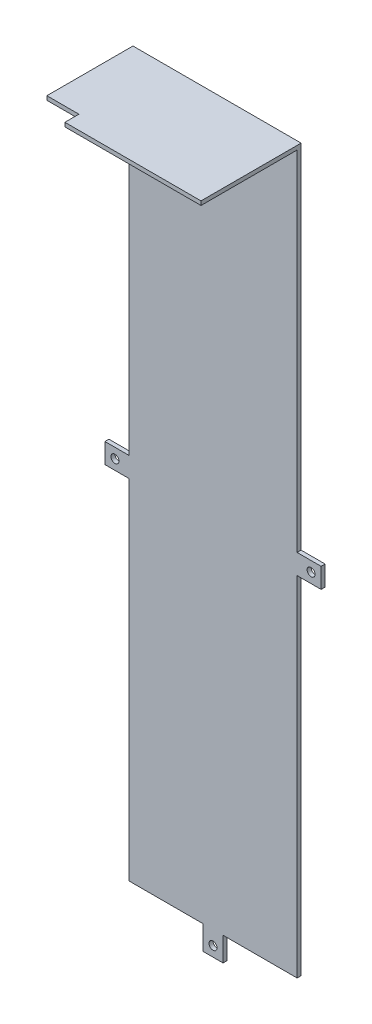
SolidWorks part; units mm, degrees
ref_plane "Alzado" through (0, 0, 0) normal (0, 0, 1) x (1, 0, 0)
ref_plane "Planta" through (0, 0, 0) normal (0, 1, 0) x (1, 0, 0)
ref_plane "Vista lateral" through (0, 0, 0) normal (1, 0, 0) x (0, 0, -1)
sketch "Sketch1" plane through (0, 0, 0) normal (0, 1, 0) x (1, 0, 0)
  line L1 (-16.6842, 5.7368) -> (25.3158, 5.7368)
  line L2 (-16.6842, 5.7368) -> (-16.6842, -19.2632)
  line L3 (-16.6842, -19.2632) -> (25.3158, -19.2632)
  line L4 (25.3158, 5.7368) -> (25.3158, -19.2632)
  dimension "D1" = 42
  dimension "D2" = 25
extrude "Boss-Extrude1" add sketch "Sketch1" along normal blind 1
sketch "Sketch2" plane through (0, 1, 0) normal (0, 1, 0) x (1, 0, 0)
  line L0 (-16.6842, 5.7368) -> (-16.6842, -19.2632) construction
  line L1 (25.3158, 5.7368) -> (-16.6842, 5.7368)
  line L2 (25.3158, 5.7368) -> (25.3158, 4.7368)
  line L3 (25.3158, 4.7368) -> (-16.6842, 4.7368)
  line L4 (-16.6842, 5.7368) -> (-16.6842, 4.7368)
  dimension "D1" = 1
extrude "Boss-Extrude2" add sketch "Sketch2" against normal blind 179
sketch "Sketch3" plane through (0, -178, 0) normal (0, -1, 0) x (1, 0, 0)
  line L1 (25.3158, -5.7368) -> (-16.6842, -5.7368)
  line L2 (25.3158, -5.7368) -> (25.3158, -4.7368)
  line L3 (25.3158, -4.7368) -> (-16.6842, -4.7368)
  line L4 (-16.6842, -5.7368) -> (-16.6842, -4.7368)
extrude "Boss-Extrude3" add sketch "Sketch3" along normal blind 2.1
sketch "Sketch4" plane through (0, 0, -4.7368) normal (0, 0, 1) x (1, 0, 0)
  line L0 (-16.6842, -180.1) -> (-16.6842, 0) construction
  line L1 (25.3158, -180.1) -> (-16.6842, -180.1)
  line L2 (25.3158, -180.1) -> (25.3158, -179.1)
  line L3 (25.3158, -179.1) -> (-16.6842, -179.1)
  line L4 (-16.6842, -180.1) -> (-16.6842, -179.1)
  dimension "D1" = 1
extrude "Boss-Extrude4" add sketch "Sketch4" along normal blind 15
sketch "Sketch6" plane through (0, -180.1, 0) normal (0, -1, 0) x (1, 0, 0)
  line L0 (-16.6842, 10.2632) -> (-16.6842, -5.7368) construction
  line L2 (25.3158, -5.7368) -> (25.3158, 10.2632) construction
  circle A0 centre (-6.6842, 3.5932) radius 1.25
  circle A1 centre (15.3158, 3.5932) radius 1.25
  dimension "D2" = 10
  dimension "D1" = 10
extrude "Cut-Extrude1" cut sketch "Sketch6" against normal blind 15
sketch "Sketch7" plane through (0, -180.1, 0) normal (0, -1, 0) x (1, 0, 0)
  line L1 (25.3158, -5.7368) -> (25.3158, 10.2632) construction
  line L2 (-16.6842, 10.2632) -> (25.3158, 10.2632)
  line L3 (-16.6842, 10.2632) -> (-16.6842, 8.5932)
  line L4 (-16.6842, 8.5932) -> (25.3158, 8.5932)
  line L5 (25.3158, 10.2632) -> (25.3158, 8.5932)
extrude "Cut-Extrude2" cut sketch "Sketch7" against normal blind 15
sketch "Sketch8" plane through (0, 1, 0) normal (0, 1, 0) x (1, 0, 0)
  line L1 (-16.6842, -19.2632) -> (-8.6842, -19.2632)
  line L2 (-16.6842, -19.2632) -> (-16.6842, -15.7632)
  line L3 (-16.6842, -15.7632) -> (-8.6842, -15.7632)
  line L4 (-8.6842, -19.2632) -> (-8.6842, -15.7632)
  dimension "D1" = 8
  dimension "D2" = 3.5
extrude "Cut-Extrude3" cut sketch "Sketch8" against normal blind 15
sketch "Sketch9" plane through (0, -180.1, 0) normal (0, -1, 0) x (1, 0, 0)
  line L1 (-16.6842, 8.5932) -> (25.3158, 8.5932)
  line L2 (-16.6842, 8.5932) -> (-16.6842, -5.7368)
  line L3 (-16.6842, -5.7368) -> (25.3158, -5.7368)
  line L4 (25.3158, 8.5932) -> (25.3158, -5.7368)
extrude "Cut-Extrude4" cut sketch "Sketch9" against normal blind 10
sketch "Sketch10" plane through (0, 0, -5.7368) normal (0, 0, -1) x (-1, 0, 0)
  line L0 (-25.3158, -170.1) -> (-6.8158, -170.1) construction
  line L1 (16.6842, -170.1) -> (-25.3158, -170.1) construction
  line L3 (-6.8158, -170.1) -> (-1.8158, -170.1)
  line L4 (-6.8158, -170.1) -> (-6.8158, -176.1)
  line L5 (-6.8158, -176.1) -> (-1.8158, -176.1)
  line L6 (-1.8158, -170.1) -> (-1.8158, -176.1)
  dimension "D1" = 18.5
  dimension "D2" = 6
  dimension "D3" = 5
extrude "Boss-Extrude5" add sketch "Sketch10" against normal blind 1
sketch "Sketch11" plane through (0, 0, -5.7368) normal (0, 0, -1) x (-1, 0, 0)
  line L0 (-6.8158, -176.1) -> (-6.8158, -171.1) construction
  line L1 (-6.8158, -170.1) -> (-6.8158, -176.1) construction
  line L2 (-6.8158, -171.1) -> (-1.8158, -171.1) construction
  line L3 (-1.8158, -176.1) -> (-1.8158, -170.1) construction
  line L4 (-1.8158, -171.1) -> (-1.8158, -176.1) construction
  line L5 (-1.8158, -176.1) -> (-6.8158, -176.1) construction
  circle A0 centre (-4.3158, -173.6) radius 1
  dimension "D1" = 5
extrude "Cut-Extrude5" cut sketch "Sketch11" against normal blind 1
sketch "Sketch12" plane through (0, -170.1, 0) normal (0, -1, 0) x (1, 0, 0)
  line L1 (25.3158, -5.7368) -> (-16.6842, -5.7368)
  line L2 (25.3158, -5.7368) -> (25.3158, -4.7368)
  line L3 (25.3158, -4.7368) -> (-16.6842, -4.7368)
  line L4 (-16.6842, -5.7368) -> (-16.6842, -4.7368)
extrude "Boss-Extrude6" add sketch "Sketch12" along normal blind 9
sketch "Sketch13" plane through (0, 0, -5.7368) normal (0, 0, -1) x (-1, 0, 0)
  line L0 (16.6842, -179.1) -> (-25.3158, -179.1) construction
  line L1 (-6.8158, -179.1) -> (-1.8158, -179.1)
  line L2 (-6.8158, -179.1) -> (-6.8158, -185.1)
  line L3 (-6.8158, -185.1) -> (-1.8158, -185.1)
  line L4 (-1.8158, -179.1) -> (-1.8158, -185.1)
  line L5 (-25.3158, 1) -> (-25.3158, -179.1) construction
  dimension "D1" = 6
  dimension "D2" = 5
  dimension "D3" = 18.5
extrude "Boss-Extrude8" add sketch "Sketch13" against normal blind 1
sketch "Sketch15" plane through (0, 0, -5.7368) normal (0, 0, -1) x (-1, 0, 0)
  line L0 (-1.8158, -185.1) -> (-1.8158, -180.1) construction
  line L1 (-1.8158, -185.1) -> (-1.8158, -179.1) construction
  line L2 (-1.8158, -180.1) -> (-6.8158, -180.1) construction
  line L3 (-6.8158, -179.1) -> (-6.8158, -185.1) construction
  line L4 (-6.8158, -180.1) -> (-6.8158, -185.1) construction
  line L5 (-6.8158, -185.1) -> (-1.8158, -185.1) construction
  circle A0 centre (-4.3158, -182.6) radius 1
  dimension "D1" = 5
extrude "Cut-Extrude7" cut sketch "Sketch15" against normal blind 1
sketch "Sketch16" plane through (0, 0, -5.7368) normal (0, 0, -1) x (-1, 0, 0)
  line L0 (-25.3158, -179.1) -> (-25.3158, -92.05) construction
  line L1 (-25.3158, 1) -> (-25.3158, -179.1) construction
  line L3 (-25.3158, -92.05) -> (-31.3158, -92.05)
  line L4 (-25.3158, -92.05) -> (-25.3158, -87.05)
  line L5 (-25.3158, -87.05) -> (-31.3158, -87.05)
  line L6 (-31.3158, -92.05) -> (-31.3158, -87.05)
  dimension "D1" = 87.05
  dimension "D2" = 6
  dimension "D3" = 5
extrude "Boss-Extrude9" add sketch "Sketch16" against normal blind 1
sketch "Sketch17" plane through (0, 0, -5.7368) normal (0, 0, -1) x (-1, 0, 0)
  line L1 (-31.3158, -87.05) -> (21.6842, -87.05)
  line L2 (-31.3158, -87.05) -> (-31.3158, -92.05)
  line L3 (-31.3158, -92.05) -> (21.6842, -92.05)
  line L4 (21.6842, -87.05) -> (21.6842, -92.05)
  dimension "D1" = 53
extrude "Boss-Extrude10" add sketch "Sketch17" against normal blind 1
sketch "Sketch18" plane through (0, 0, -5.7368) normal (0, 0, -1) x (-1, 0, 0)
  line L0 (-31.3158, -87.05) -> (-26.3158, -87.05) construction
  line L1 (-25.3158, -87.05) -> (-31.3158, -87.05) construction
  line L2 (-26.3158, -87.05) -> (-26.3158, -92.05) construction
  line L3 (-31.3158, -92.05) -> (-25.3158, -92.05) construction
  line L4 (-26.3158, -92.05) -> (-31.3158, -92.05) construction
  line L5 (-31.3158, -92.05) -> (-31.3158, -87.05) construction
  circle A0 centre (-28.8158, -89.55) radius 1
  dimension "D1" = 5
extrude "Cut-Extrude8" cut sketch "Sketch18" against normal blind 1
sketch "Sketch20" plane through (-21.6842, 0, 0) normal (-1, 0, 0) x (0, 0, 1)
  line L1 (-5.7368, -87.05) -> (-4.7368, -87.05)
  line L2 (-5.7368, -87.05) -> (-5.7368, -92.05)
  line L3 (-5.7368, -92.05) -> (-4.7368, -92.05)
  line L4 (-4.7368, -87.05) -> (-4.7368, -92.05)
extrude "Boss-Extrude11" add sketch "Sketch20" along normal blind 1
sketch "Sketch21" plane through (0, 0, -5.7368) normal (0, 0, -1) x (-1, 0, 0)
  line L0 (22.6842, -87.05) -> (17.6842, -87.05) construction
  line L1 (22.6842, -87.05) -> (16.6842, -87.05) construction
  line L2 (17.6842, -87.05) -> (17.6842, -92.05) construction
  line L3 (16.6842, -92.05) -> (22.6842, -92.05) construction
  line L4 (17.6842, -92.05) -> (22.6842, -92.05) construction
  line L5 (22.6842, -92.05) -> (22.6842, -87.05) construction
  circle A0 centre (20.1842, -89.55) radius 1
  dimension "D2" = 2.5
  dimension "D1" = 5
extrude "Cut-Extrude9" cut sketch "Sketch21" against normal blind 1
